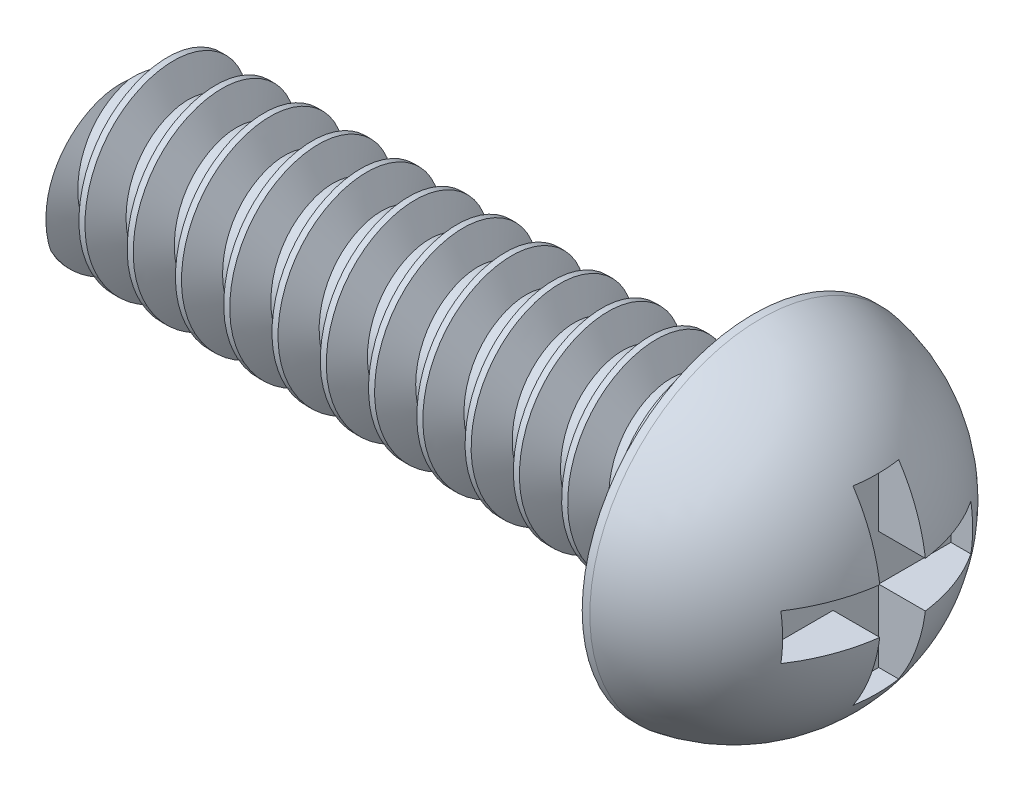
SolidWorks part; units mm, degrees
material "Zinc AC41A Alloy, As Cast"
ref_plane "Front Plane" through (0, 0, 0) normal (0, 0, 1) x (1, 0, 0)
ref_plane "Top Plane" through (0, 0, 0) normal (0, 1, 0) x (1, 0, 0)
ref_plane "Right Plane" through (0, 0, 0) normal (1, 0, 0) x (0, 0, -1)
sketch "Sketch1" plane through (0, 0, 0) normal (1, 0, 0) x (0, 0, -1)
  circle A0 centre (0, 0) radius 1.225
  dimension "D1" = 2.45
extrude "Boss-Extrude1" add sketch "Sketch1" along normal blind 9.15
sketch "Sketch2" plane through (9.15, 0, 0) normal (1, 0, 0) x (0, 0, -1)
  circle A0 centre (0, 0) radius 2.25
  dimension "D1" = 4.5
extrude "Boss-Extrude2" add sketch "Sketch2" along normal blind 0.1
sketch "Sketch3" plane through (0, 0, 0) normal (0, 1, 0) x (1, 0, 0)
  line L0 (9.25, 0) -> (11.15, 0)
  line L1 (9.25, -2.25) -> (9.25, 2.25) construction
  line L2 (9.25, -2.25) -> (9.25, 0)
  arc A0 (9.25, -2.25) -> (11.15, 0) centre (8.8939, -0.022) ccw
revolve "Revolve1" add sketch "Sketch3" angle 360 about L0
ref_plane "Plane1" through (12, 0, 0) normal (1, 0, 0) x (0, 0, -1)
sketch "Sketch4" plane through (12, 0, 0) normal (1, 0, 0) x (0, 0, -1)
  line L0 (0, 1.25) -> (0, -1.25) construction
  line L1 (-1.25, 0) -> (1.25, 0) construction
  line L2 (-1.25, -0.3) -> (-0.3, -0.3)
  line L3 (-1.25, 0.3) -> (-0.3, 0.3)
  line L4 (-0.3, 1.25) -> (-0.3, 0.3)
  line L5 (0.3, 1.25) -> (0.3, 0.3)
  line L6 (0.3, 1.25) -> (-0.3, 1.25)
  line L7 (-0.3, -1.25) -> (0.3, -1.25)
  line L8 (1.25, 0.3) -> (1.25, -0.3)
  line L9 (-1.25, 0.3) -> (-1.25, -0.3)
  line L10 (0.3, -0.3) -> (0.3, -1.25)
  line L11 (0.3, 1.25) -> (0.3, -1.25) construction
  line L12 (0.3, 0.3) -> (1.25, 0.3)
  line L13 (-1.25, 0.3) -> (1.25, 0.3) construction
  line L14 (-0.3, -0.3) -> (-0.3, -1.25)
  line L15 (-0.3, 1.25) -> (-0.3, -1.25) construction
  line L16 (0.3, -0.3) -> (1.25, -0.3)
  line L17 (-1.25, -0.3) -> (1.25, -0.3) construction
  point P4 (0, 0)
  point P8 (0, 0)
  dimension "D1" = 0.3
  dimension "D2" = 0.3
  dimension "D3" = 0.3
  dimension "D4" = 0.3
extrude "Cut-Extrude1" cut sketch "Sketch4" against normal blind 1.5
thread "Thread1" pitch 0.635 method cut profile "Thread Profile1" start angle 0, offset 0, length 0, pitch 0.635, diameter 2.45
ref_plane "Plane2" through (0, 0, -1.225) normal (0, -1, 0) x (0, 0, -1)
sketch "Thread Profile1" plane through (0, 0, -1.225) normal (0, -1, 0) x (0, 0, -1)
  line L0 (0, 0) -> (0, 0.635) construction
  line L11 (0, 0) -> (0, 0.5556)
  line L12 (0, 0.5556) -> (-0.3437, 0.3572)
  line L13 (-0.3437, 0.3572) -> (-0.3437, 0.1984)
  line L15 (-0.3437, 0.1984) -> (0, 0)
  line L17 (-0.3437, 0.2778) -> (0, 0.2778) construction
  point P2 (0, 0)
  dimension "Pitch" = 0.635
  dimension "Profile_Angle" = 60
  dimension "Profile_Land" = 0.1588
  dimension "Profile_Height" = 0.3437
sketch "Sketch7" plane through (0, 0, 0) normal (-1, 0, 0) x (0, 0, 1)
  line L1 (1.6147, -1.5317) -> (-1.6147, -1.5317)
  line L2 (1.6147, -1.5317) -> (1.6147, 1.5317)
  line L3 (1.6147, 1.5317) -> (-1.6147, 1.5317)
  line L4 (-1.6147, -1.5317) -> (-1.6147, 1.5317)
  line L5 (1.6147, -1.5317) -> (-1.6147, 1.5317) construction
  line L6 (1.6147, 1.5317) -> (-1.6147, -1.5317) construction
  point P0 (0, 0)
extrude "Cut-Extrude2" cut sketch "Sketch7" against normal blind 1
